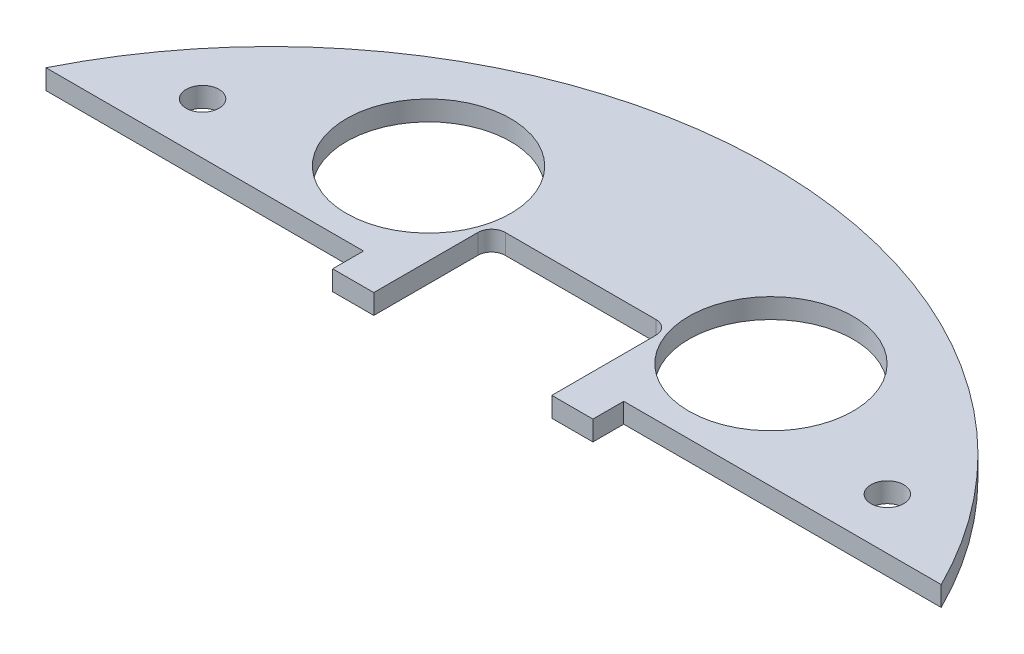
SolidWorks part; units mm, degrees
material "Acrylic (Medium-high impact)"
ref_plane "Front Plane" through (0, 0, 0) normal (0, 0, 1) x (1, 0, 0)
ref_plane "Top Plane" through (0, 0, 0) normal (0, 1, 0) x (1, 0, 0)
ref_plane "Right Plane" through (0, 0, 0) normal (1, 0, 0) x (0, 0, -1)
sketch "Sketch1" plane through (0, 0, 0) normal (0, 1, 0) x (1, 0, 0)
  line L0 (0, -85) -> (-32.7511, -65.2408) construction
  line L1 (0, -85) -> (0, 0) construction
  arc A0 (36.8566, -63.0126) -> (-36.8566, -63.0126) centre (0, 0) ccw
  arc A1 (30.3631, -61.7375) -> (-30.3631, -61.7375) centre (0, -85) ccw
  arc A2 (36.8566, -63.0126) -> (30.3631, -61.7375) centre (34.3322, -58.6967) cw
  arc A3 (-30.3631, -61.7375) -> (-36.8566, -63.0126) centre (-34.3322, -58.6967) cw
  dimension "D1" = 146
  dimension "D2" = 76.5
  dimension "D4" = 5
  dimension "D3" = 85
extrude "Boss-Extrude1" add sketch "Sketch1" along normal blind 2.9
sketch "solenoid placement" plane through (0, 2.9, 0) normal (0, 1, 0) x (1, 0, 0)
  line L4 (-19, -36) -> (19, -36)
  line L5 (-19, -36) -> (19, -36)
  line L6 (19, -36) -> (19, 28)
  line L7 (19, -36) -> (19, 28)
  line L8 (19, 28) -> (-19, 28)
  line L9 (19, 28) -> (-19, 28)
  line L10 (-19, 28) -> (-19, -36)
  line L11 (-19, 28) -> (-19, -36)
  circle A1 centre (0, 0) radius 73 construction
  arc A2 (36.8566, -63.0126) -> (-36.8566, -63.0126) centre (0, 0) ccw construction
  dimension "D1" = 0
extrude "Cut-Extrude1" cut sketch "solenoid placement" against normal through all
sketch "Sketch4" plane through (0, 2.9, 0) normal (0, 1, 0) x (1, 0, 0)
  line L1 (-13, 28) -> (13, 28)
  line L2 (-13, 28) -> (-13, 43.2)
  line L3 (13, 45.2) -> (-13, 45.2) construction
  line L4 (13, 28) -> (13, 43.2)
  line L5 (11, 45.2) -> (-11, 45.2)
  line L6 (19, 28) -> (-19, 28) construction
  arc A0 (11, 45.2) -> (13, 43.2) centre (11, 43.2) cw
  arc A1 (-11, 45.2) -> (-13, 43.2) centre (-11, 43.2) ccw
  point P4 (13, 28)
  point P6 (0, 28)
  point P14 (0, 0)
  dimension "D1" = 2
extrude "Cut-Extrude4" cut sketch "Sketch4" against normal through all
sketch "Sketch5" plane through (0, 2.9, 0) normal (0, 1, 0) x (1, 0, 0)
  circle A2 centre (-25, 48) radius 12
  circle A3 centre (-25, 48) radius 12
  circle A4 centre (25, 48) radius 12
  circle A21 centre (25, 48) radius 12
  dimension "D1" = 0
  dimension "D2" = 0
extrude "Cut-Extrude5" cut sketch "Sketch5" against normal through all
sketch "Sketch6" plane through (0, 2.9, 0) normal (0, 1, 0) x (1, 0, 0)
  circle A1 centre (40, -40) radius 2.4
  circle A2 centre (40, -40) radius 2.4
  circle A3 centre (-40, -40) radius 2.4
  circle A4 centre (-40, -40) radius 2.4
  circle A5 centre (-50, 40) radius 2.4
  circle A6 centre (-50, 40) radius 2.4
  circle A7 centre (50, 40) radius 2.4
  circle A8 centre (50, 40) radius 2.4
  dimension "D1" = 0
  dimension "D2" = 0
  dimension "D3" = 0
  dimension "D4" = 0
extrude "Cut-Extrude6" cut sketch "Sketch6" against normal through all
sketch "Sketch3" plane through (0, 2.9, 0) normal (0, 1, 0) x (1, 0, 0)
  line L0 (-19, 28) -> (19, 28)
  line L1 (-73, -32.5) -> (73, -32.5)
  line L2 (-73, -32.5) -> (-73, 32.5)
  line L3 (-73, 32.5) -> (-19, 32.5)
  line L4 (73, -32.5) -> (73, 32.5)
  line L5 (-73, -32.5) -> (73, 32.5) construction
  line L6 (-73, 32.5) -> (73, -32.5) construction
  line L7 (19, 28) -> (19, 32.5)
  line L8 (-19, 28) -> (-19, 32.5)
  line L9 (19, 32.5) -> (73, 32.5)
  arc A0 (36.8566, -63.0126) -> (-36.8566, -63.0126) centre (0, 0) ccw construction
  point P0 (0, 0)
  point P10 (0, 0)
  point P13 (-18.9045, 28)
  point P17 (0, 0)
  point P18 (19, 28)
  point P20 (-19, 28)
  dimension "D1" = 65
extrude "Cut-Extrude3" cut sketch "Sketch3" against normal through all
delete or keep bodies "Body-Delete/Keep 1" type delete bodies bodies 115
equation "\"smallPulleyTeeth\"= 15"
equation "\"largePulleyTeeth\"= 30"
equation "\"eighthThick\"= 2.9mm"
equation "\"sixteenthThick\" = 1.7mm"
equation "\"quarterThick\"=6.0mm"
equation "\"OD\" = 146mm"
equation "\"puckAngle\" = 60.5deg"
equation "\"D1@Sketch1\"=\"OD\""
equation "\"puckDiam\" = 76.5mm"
equation "\"D2@Sketch1\"=\"puckDiam\""
equation "\"D1@Boss-Extrude1\"=\"eighthThick\""
equation "\"axlePress\" = 5.9mm"
equation "\"press\" = 0.2mm"
equation "\"wheelClear\" = 0.3mm"
equation "\"10-32clear\" = 4.8mm"
equation "\"6-32clear\" = 3.3mm"
equation "\"8-32clear\" = 4.0mm"
equation "\"wheelHeight\" = 22mm"
equation "\"wheelWell\" = 65mm"
equation "\"D1@Sketch3\"=\"wheelWell\""
equation "\"puckDist\" = 85mm"
equation "\"scoopFillet\" = 5mm"
equation "\"4-40clear\" = 3.0mm"
equation "\"D3@Sketch1\"=\"puckDist\""
equation "\"D4@Sketch1\"=\"scoopFillet\""
